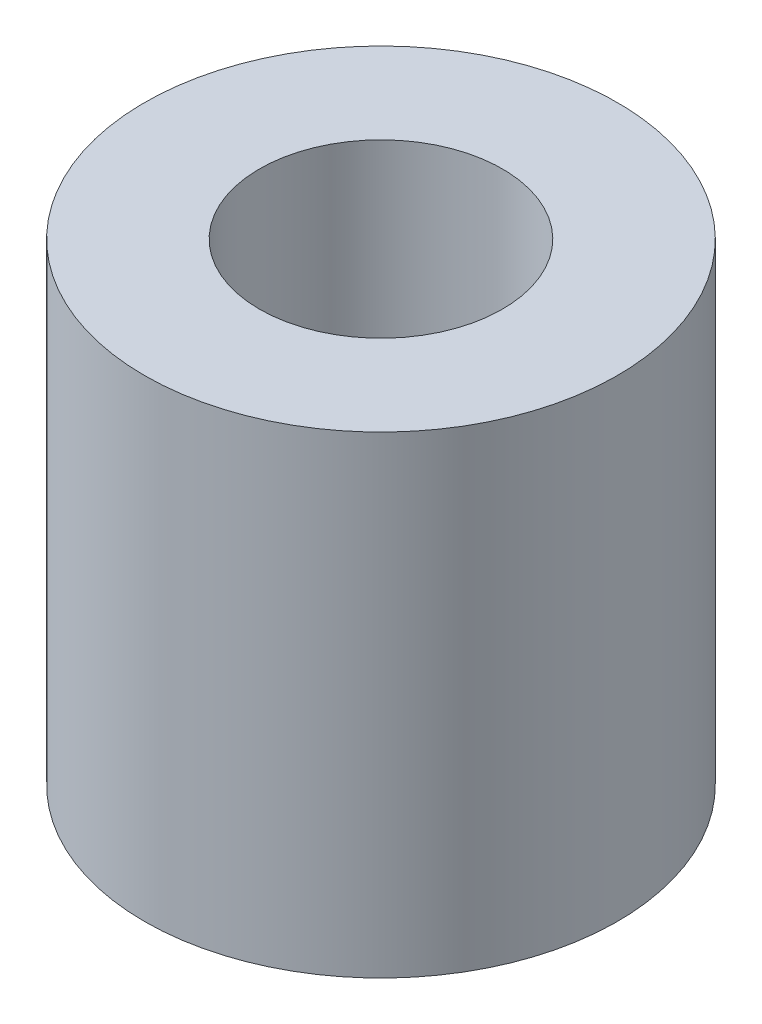
SolidWorks part; units mm, degrees
material "PLA"
ref_plane "Front Plane" through (0, 0, 0) normal (0, 0, 1) x (1, 0, 0)
ref_plane "Top Plane" through (0, 0, 0) normal (0, 1, 0) x (1, 0, 0)
ref_plane "Right Plane" through (0, 0, 0) normal (1, 0, 0) x (0, 0, -1)
sketch "Sketch1" plane through (0, 0, 0) normal (0, 1, 0) x (1, 0, 0)
  circle A0 centre (0, 0) radius 6.35
  circle A1 centre (0, 0) radius 3.2639
  dimension "D1" = 12.7
  dimension "D2" = 6.5278
extrude "Boss-Extrude1" add sketch "Sketch1" along normal blind 12.7
